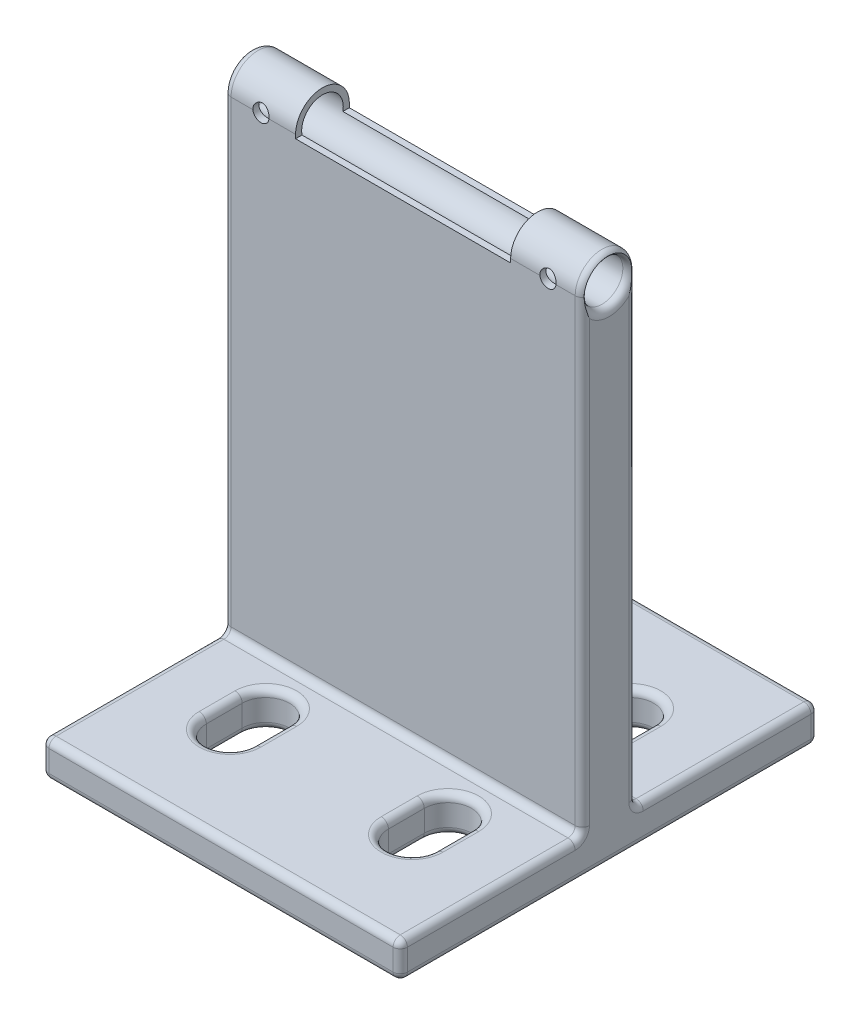
SolidWorks part; units mm, degrees
ref_plane "Front Plane" through (0, 0, 0) normal (0, 0, 1) x (1, 0, 0)
ref_plane "Top Plane" through (0, 0, 0) normal (0, 1, 0) x (1, 0, 0)
ref_plane "Right Plane" through (0, 0, 0) normal (1, 0, 0) x (0, 0, -1)
sketch "Sketch1" plane through (0, 0, 0) normal (1, 0, 0) x (0, 0, -1)
  line L0 (-4.3217, 53.5211) -> (-4.3217, -16.4789) construction
  line L2 (-8.0717, 6.7606) -> (-8.0717, -16.4789)
  line L3 (-8.0717, -16.4789) -> (-0.5717, -16.4789)
  line L4 (-0.5717, 6.7606) -> (-0.5717, -16.4789)
  line L5 (-8.0717, 53.5211) -> (-8.0717, 6.7606)
  line L6 (-0.5717, 53.5211) -> (-0.5717, 6.7606)
  arc A0 (-0.5717, 53.5211) -> (-8.0717, 53.5211) centre (-4.3217, 53.5211) ccw
  circle A1 centre (-4.3217, 53.5211) radius 2.9
  dimension "D2" = 5.8
  dimension "D1" = 7.5
  dimension "D3" = 70
extrude "Boss-Extrude1" add sketch "Sketch1" along normal blind 50
sketch "Sketch2" plane through (0, 0, 8.0717) normal (0, 0, 1) x (1, 0, 0)
  line L0 (0, 53.5211) -> (50, 53.5211) construction
  line L1 (10, 59.1126) -> (40, 59.1126)
  line L2 (10, 59.1126) -> (10, 52.9834)
  line L3 (10, 52.9834) -> (40, 52.9834)
  line L4 (40, 59.1126) -> (40, 52.9834)
  line L5 (10, 53.5211) -> (40, 53.5211) construction
  point P10 (25, 53.5211)
  dimension "D1" = 30
extrude "Cut-Extrude1" cut sketch "Sketch2" against normal blind 50
sketch "Sketch3" plane through (0, 0, 8.0717) normal (0, 0, 1) x (1, 0, 0)
  line L0 (50, 53.5211) -> (50, -16.4789) construction
  line L1 (0, -16.4789) -> (50, -16.4789)
  line L2 (0, -16.4789) -> (0, -11.4789)
  line L3 (0, -11.4789) -> (50, -11.4789)
  line L4 (50, -16.4789) -> (50, -11.4789)
  dimension "D1" = 5
extrude "Boss-Extrude2" add sketch "Sketch3" along normal blind 25.4 and the other way blind 32.9
sketch "Sketch4" plane through (0, -16.4789, 0) normal (0, -1, 0) x (1, 0, 0)
  line L0 (50, -24.8283) -> (0, 33.4717) construction
  line L1 (37.7, -8.3783) -> (12.3, -8.3783) construction
  line L2 (37.7, -8.3783) -> (37.7, 17.0217) construction
  line L3 (37.7, 17.0217) -> (12.3, 17.0217) construction
  line L4 (12.3, -8.3783) -> (12.3, 17.0217) construction
  line L5 (37.7, -8.3783) -> (12.3, 17.0217) construction
  line L6 (37.7, -10.8783) -> (37.7, -5.8783) construction
  line L7 (34.4, -10.8783) -> (34.4, -5.8783)
  line L8 (41, -10.8783) -> (41, -5.8783)
  line L9 (12.3, -10.8783) -> (12.3, -5.8783) construction
  line L10 (9, -10.8783) -> (9, -5.8783)
  line L11 (15.6, -10.8783) -> (15.6, -5.8783)
  line L12 (37.7, 14.5217) -> (37.7, 19.5217) construction
  line L13 (34.4, 14.5217) -> (34.4, 19.5217)
  line L14 (41, 14.5217) -> (41, 19.5217)
  line L15 (12.3, 14.5217) -> (12.3, 19.5217) construction
  line L16 (9, 14.5217) -> (9, 19.5217)
  line L17 (15.6, 14.5217) -> (15.6, 19.5217)
  arc A0 (34.4, -10.8783) -> (41, -10.8783) centre (37.7, -10.8783) ccw
  arc A1 (41, -5.8783) -> (34.4, -5.8783) centre (37.7, -5.8783) ccw
  arc A2 (9, -10.8783) -> (15.6, -10.8783) centre (12.3, -10.8783) ccw
  arc A3 (15.6, -5.8783) -> (9, -5.8783) centre (12.3, -5.8783) ccw
  arc A4 (34.4, 14.5217) -> (41, 14.5217) centre (37.7, 14.5217) ccw
  arc A5 (41, 19.5217) -> (34.4, 19.5217) centre (37.7, 19.5217) ccw
  arc A6 (9, 14.5217) -> (15.6, 14.5217) centre (12.3, 14.5217) ccw
  arc A7 (15.6, 19.5217) -> (9, 19.5217) centre (12.3, 19.5217) ccw
  point P8 (25, 4.3217)
  point P11 (37.7, -8.3783)
  point P16 (12.3, -8.3783)
  point P23 (37.7, 17.0217)
  point P30 (12.3, 17.0217)
  dimension "D2" = 3.3
  dimension "D3" = 25.4
  dimension "D1" = 25.4
  dimension "D6" = 5
extrude "Cut-Extrude2" cut sketch "Sketch4" against normal blind 25.4
sketch "4-40 screw" plane through (0, 0, 0) normal (0, 0, 1) x (1, 0, 0)
  circle A0 centre (45.2027, 53.6472) radius 1.1303
  circle A1 centre (5.1658, 53.6472) radius 1.1303
  dimension "D1" = 2.2606
extrude "Cut-Extrude5" cut sketch "4-40 screw" along normal through all
fillet "Fillet2" radius 1 56 edges at (50, 21.0211, 8.0717) (0, 21.0211, 8.0717) (50, 21.0211, 0.5717) (0, 21.0211, 0.5717) (50, -11.4789, 20.7717) (25, -11.4789, 33.4717) (0, -11.4789, 20.7717) (25, -11.4789, 8.0717) (34.4, -11.4789, 17.0217) (37.7, -11.4789, 22.8217) (41, -11.4789, 17.0217) (37.7, -11.4789, 11.2217) (9, -11.4789, 17.0217) (12.3, -11.4789, 22.8217) (15.6, -11.4789, 17.0217) (12.3, -11.4789, 11.2217) (0, -11.4789, -12.1283) (25, -11.4789, -24.8283) (50, -11.4789, -12.1283) (25, -11.4789, 0.5717) (34.4, -11.4789, -8.3783) (37.7, -11.4789, -2.5783) (41, -11.4789, -8.3783) (37.7, -11.4789, -14.1783) (9, -11.4789, -8.3783) (12.3, -11.4789, -2.5783) (15.6, -11.4789, -8.3783) (12.3, -11.4789, -14.1783) (50, 53.5211, 1.4217) (0, 53.5211, 1.4217) (50, 57.2711, 4.3217) (0, 57.2711, 4.3217) (0, -13.9789, 33.4717) (50, -13.9789, 33.4717) (50, -13.9789, -24.8283) (0, -13.9789, -24.8283) (25, -16.4789, 33.4717) (50, -16.4789, 4.3217) (25, -16.4789, -24.8283) (0, -16.4789, 4.3217) (37.7, -16.4789, -2.5783) (34.4, -16.4789, -8.3783) (37.7, -16.4789, -14.1783) (41, -16.4789, -8.3783) (12.3, -16.4789, -2.5783) (9, -16.4789, -8.3783) (12.3, -16.4789, -14.1783) (15.6, -16.4789, -8.3783) (37.7, -16.4789, 22.8217) (34.4, -16.4789, 17.0217) (37.7, -16.4789, 11.2217) (41, -16.4789, 17.0217) (12.3, -16.4789, 22.8217) (9, -16.4789, 17.0217) (12.3, -16.4789, 11.2217) (15.6, -16.4789, 17.0217)
